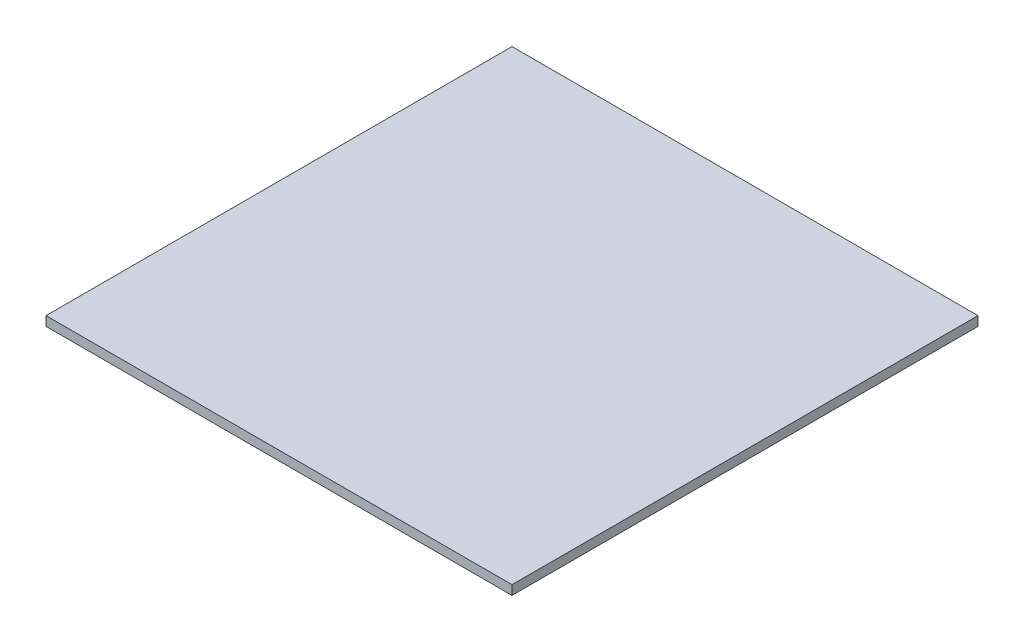
SolidWorks part; units mm, degrees
material "Perspex (TM) GS Acrylic Cast Sheet"
ref_plane "Front Plane" through (0, 0, 0) normal (0, 0, 1) x (1, 0, 0)
ref_plane "Top Plane" through (0, 0, 0) normal (0, 1, 0) x (1, 0, 0)
ref_plane "Right Plane" through (0, 0, 0) normal (1, 0, 0) x (0, 0, -1)
sketch "Sketch1" plane through (0, 0, 0) normal (0, 1, 0) x (1, 0, 0)
  line L1 (-100, -100) -> (100, -100)
  line L2 (-100, -100) -> (-100, 100)
  line L3 (-100, 100) -> (100, 100)
  line L4 (100, -100) -> (100, 100)
  line L5 (-100, -100) -> (100, 100) construction
  line L6 (-100, 100) -> (100, -100) construction
  point P0 (0, 0)
  dimension "D1" = 200
  dimension "D2" = 200
extrude "Boss-Extrude1" add sketch "Sketch1" along normal blind 4
sketch "Sketch2" plane through (0, 0, 0) normal (0, -1, 0) x (-1, 0, 0)
  line L1 (96, 96) -> (-96, 96)
  line L2 (96, 96) -> (96, -96)
  line L3 (96, -96) -> (-96, -96)
  line L4 (-96, 96) -> (-96, -96)
  line L5 (96, 96) -> (-96, -96) construction
  line L6 (96, -96) -> (-96, 96) construction
  point P0 (0, 0)
  dimension "D1" = 192
  dimension "D2" = 192
extrude "Boss-Extrude2" add sketch "Sketch2" along normal blind 4
